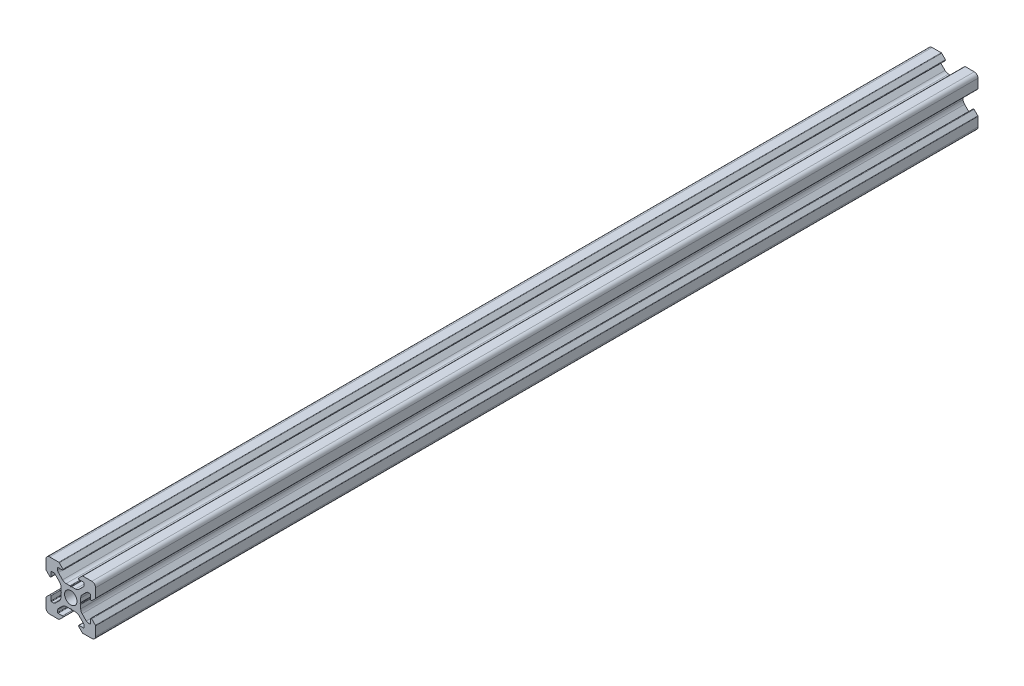
SolidWorks part; units mm, degrees
material "6063-T5"
ref_plane "Спереди" through (0, 0, 0) normal (0, 0, 1) x (1, 0, 0)
ref_plane "Сверху" through (0, 0, 0) normal (0, 1, 0) x (1, 0, 0)
ref_plane "Справа" through (0, 0, 0) normal (1, 0, 0) x (0, 0, -1)
sketch "Model" plane through (0, 0, 0) normal (0, 0, 1) x (1, 0, 0)
  line L0 (-4, 0.3377) -> (-4, 1.8988)
  line L1 (-4.5858, 3.313) -> (-6.2799, 5.0071)
  line L2 (-6.987, 5.3) -> (-7.8, 5.3)
  line L3 (-8, 5.1) -> (-8, 3.33)
  line L4 (-9.9268, 4.6532) -> (-8.4268, 3.1532)
  line L5 (-10, 4.83) -> (-10, 8.5)
  line L6 (-4.6532, 9.9268) -> (-3.1532, 8.4268)
  line L7 (-0.1815, 3.9452) -> (0, 3.8)
  line L8 (0.1815, 3.9452) -> (0, 3.8)
  line L9 (0.3377, 4) -> (1.8988, 4)
  line L10 (3.313, 4.5858) -> (5.0071, 6.2799)
  line L11 (5.3, 6.987) -> (5.3, 7.8)
  line L12 (5.1, 8) -> (3.33, 8)
  line L13 (4.6532, 9.9268) -> (3.1532, 8.4268)
  line L14 (4.83, 10) -> (8.5, 10)
  line L15 (10, 4.83) -> (10, 8.5)
  line L16 (9.9268, 4.6532) -> (8.4268, 3.1532)
  line L17 (8, 5.1) -> (8, 3.33)
  line L18 (6.987, 5.3) -> (7.8, 5.3)
  line L19 (4.5858, 3.313) -> (6.2799, 5.0071)
  line L20 (4, 0.3377) -> (4, 1.8988)
  line L21 (3.9452, 0.1815) -> (3.8, 0)
  line L22 (3.9452, -0.1815) -> (3.8, 0)
  line L23 (4, -0.3377) -> (4, -1.8988)
  line L24 (4.5858, -3.313) -> (6.2799, -5.0071)
  line L25 (6.987, -5.3) -> (7.8, -5.3)
  line L26 (8, -5.1) -> (8, -3.33)
  line L27 (9.9268, -4.6532) -> (8.4268, -3.1532)
  line L28 (10, -4.83) -> (10, -8.5)
  line L29 (4.83, -10) -> (8.5, -10)
  line L30 (4.6532, -9.9268) -> (3.1532, -8.4268)
  line L31 (5.1, -8) -> (3.33, -8)
  line L32 (5.3, -6.987) -> (5.3, -7.8)
  line L33 (3.313, -4.5858) -> (5.0071, -6.2799)
  line L34 (0.3377, -4) -> (1.8988, -4)
  line L35 (0.1815, -3.9452) -> (0, -3.8)
  line L36 (-0.1815, -3.9452) -> (0, -3.8)
  line L37 (-3.313, -4.5858) -> (-5.0071, -6.2799)
  line L38 (-5.3, -6.987) -> (-5.3, -7.8)
  line L39 (-5.1, -8) -> (-3.33, -8)
  line L40 (-4.6532, -9.9268) -> (-3.1532, -8.4268)
  line L41 (-4.83, -10) -> (-8.5, -10)
  line L42 (-10, -4.83) -> (-10, -8.5)
  line L43 (-9.9268, -4.6532) -> (-8.4268, -3.1532)
  line L44 (-8, -5.1) -> (-8, -3.33)
  line L45 (-6.987, -5.3) -> (-7.8, -5.3)
  line L46 (-4.5858, -3.313) -> (-6.2799, -5.0071)
  line L47 (-4, -0.3377) -> (-4, -1.8988)
  line L48 (-3.9452, -0.1815) -> (-3.8, 0)
  line L49 (-3.9452, 0.1815) -> (-3.8, 0)
  line L50 (-0.3377, -4) -> (-1.8988, -4)
  line L51 (-0.3377, 4) -> (-1.8988, 4)
  line L52 (-3.313, 4.5858) -> (-5.0071, 6.2799)
  line L53 (-5.3, 6.987) -> (-5.3, 7.8)
  line L54 (-5.1, 8) -> (-3.33, 8)
  line L55 (-4.83, 10) -> (-8.5, 10)
  arc A0 (-4, 0.3377) -> (-3.9452, 0.1815) centre (-3.75, 0.3377) ccw
  arc A1 (-4, 1.8988) -> (-4.5858, 3.313) centre (-6, 1.8988) ccw
  arc A2 (-6.2799, 5.0071) -> (-6.987, 5.3) centre (-6.987, 4.3) ccw
  arc A3 (-7.8, 5.3) -> (-8, 5.1) centre (-7.8, 5.1) ccw
  arc A4 (-8.4268, 3.1532) -> (-8, 3.33) centre (-8.25, 3.33) ccw
  arc A5 (-10, 4.83) -> (-9.9268, 4.6532) centre (-9.75, 4.83) ccw
  arc A6 (-8.5, 10) -> (-10, 8.5) centre (-8.5, 8.5) ccw
  arc A7 (-4.6532, 9.9268) -> (-4.83, 10) centre (-4.83, 9.75) ccw
  arc A8 (-3.33, 8) -> (-3.1532, 8.4268) centre (-3.33, 8.25) ccw
  arc A9 (-5.1, 8) -> (-5.3, 7.8) centre (-5.1, 7.8) ccw
  arc A10 (-5.3, 6.987) -> (-5.0071, 6.2799) centre (-4.3, 6.987) ccw
  arc A11 (-3.313, 4.5858) -> (-1.8988, 4) centre (-1.8988, 6) ccw
  arc A12 (-0.1815, 3.9452) -> (-0.3377, 4) centre (-0.3377, 3.75) ccw
  arc A13 (0.3377, 4) -> (0.1815, 3.9452) centre (0.3377, 3.75) ccw
  arc A14 (1.8988, 4) -> (3.313, 4.5858) centre (1.8988, 6) ccw
  arc A15 (5.0071, 6.2799) -> (5.3, 6.987) centre (4.3, 6.987) ccw
  arc A16 (5.3, 7.8) -> (5.1, 8) centre (5.1, 7.8) ccw
  arc A17 (3.1532, 8.4268) -> (3.33, 8) centre (3.33, 8.25) ccw
  arc A18 (4.83, 10) -> (4.6532, 9.9268) centre (4.83, 9.75) ccw
  arc A19 (10, 8.5) -> (8.5, 10) centre (8.5, 8.5) ccw
  arc A20 (9.9268, 4.6532) -> (10, 4.83) centre (9.75, 4.83) ccw
  arc A21 (8, 3.33) -> (8.4268, 3.1532) centre (8.25, 3.33) ccw
  arc A22 (8, 5.1) -> (7.8, 5.3) centre (7.8, 5.1) ccw
  arc A23 (6.987, 5.3) -> (6.2799, 5.0071) centre (6.987, 4.3) ccw
  arc A24 (4.5858, 3.313) -> (4, 1.8988) centre (6, 1.8988) ccw
  arc A25 (3.9452, 0.1815) -> (4, 0.3377) centre (3.75, 0.3377) ccw
  arc A26 (4, -0.3377) -> (3.9452, -0.1815) centre (3.75, -0.3377) ccw
  arc A27 (4, -1.8988) -> (4.5858, -3.313) centre (6, -1.8988) ccw
  arc A28 (6.2799, -5.0071) -> (6.987, -5.3) centre (6.987, -4.3) ccw
  arc A29 (7.8, -5.3) -> (8, -5.1) centre (7.8, -5.1) ccw
  arc A30 (8.4268, -3.1532) -> (8, -3.33) centre (8.25, -3.33) ccw
  arc A31 (10, -4.83) -> (9.9268, -4.6532) centre (9.75, -4.83) ccw
  arc A32 (8.5, -10) -> (10, -8.5) centre (8.5, -8.5) ccw
  arc A33 (4.6532, -9.9268) -> (4.83, -10) centre (4.83, -9.75) ccw
  arc A34 (3.33, -8) -> (3.1532, -8.4268) centre (3.33, -8.25) ccw
  arc A35 (5.1, -8) -> (5.3, -7.8) centre (5.1, -7.8) ccw
  arc A36 (5.3, -6.987) -> (5.0071, -6.2799) centre (4.3, -6.987) ccw
  arc A37 (3.313, -4.5858) -> (1.8988, -4) centre (1.8988, -6) ccw
  arc A38 (0.1815, -3.9452) -> (0.3377, -4) centre (0.3377, -3.75) ccw
  arc A39 (-0.3377, -4) -> (-0.1815, -3.9452) centre (-0.3377, -3.75) ccw
  arc A40 (-1.8988, -4) -> (-3.313, -4.5858) centre (-1.8988, -6) ccw
  arc A41 (-5.0071, -6.2799) -> (-5.3, -6.987) centre (-4.3, -6.987) ccw
  arc A42 (-5.3, -7.8) -> (-5.1, -8) centre (-5.1, -7.8) ccw
  arc A43 (-3.1532, -8.4268) -> (-3.33, -8) centre (-3.33, -8.25) ccw
  arc A44 (-4.83, -10) -> (-4.6532, -9.9268) centre (-4.83, -9.75) ccw
  arc A45 (-10, -8.5) -> (-8.5, -10) centre (-8.5, -8.5) ccw
  arc A46 (-9.9268, -4.6532) -> (-10, -4.83) centre (-9.75, -4.83) ccw
  arc A47 (-8, -3.33) -> (-8.4268, -3.1532) centre (-8.25, -3.33) ccw
  arc A48 (-8, -5.1) -> (-7.8, -5.3) centre (-7.8, -5.1) ccw
  arc A49 (-6.987, -5.3) -> (-6.2799, -5.0071) centre (-6.987, -4.3) ccw
  arc A50 (-4.5858, -3.313) -> (-4, -1.8988) centre (-6, -1.8988) ccw
  arc A51 (-3.9452, -0.1815) -> (-4, -0.3377) centre (-3.75, -0.3377) ccw
  circle A52 centre (0, 0) radius 2.5
  dimension "D1" = 20
  dimension "D2" = 20
extrude "Extrude body" add sketch "Model" along normal blind 356
